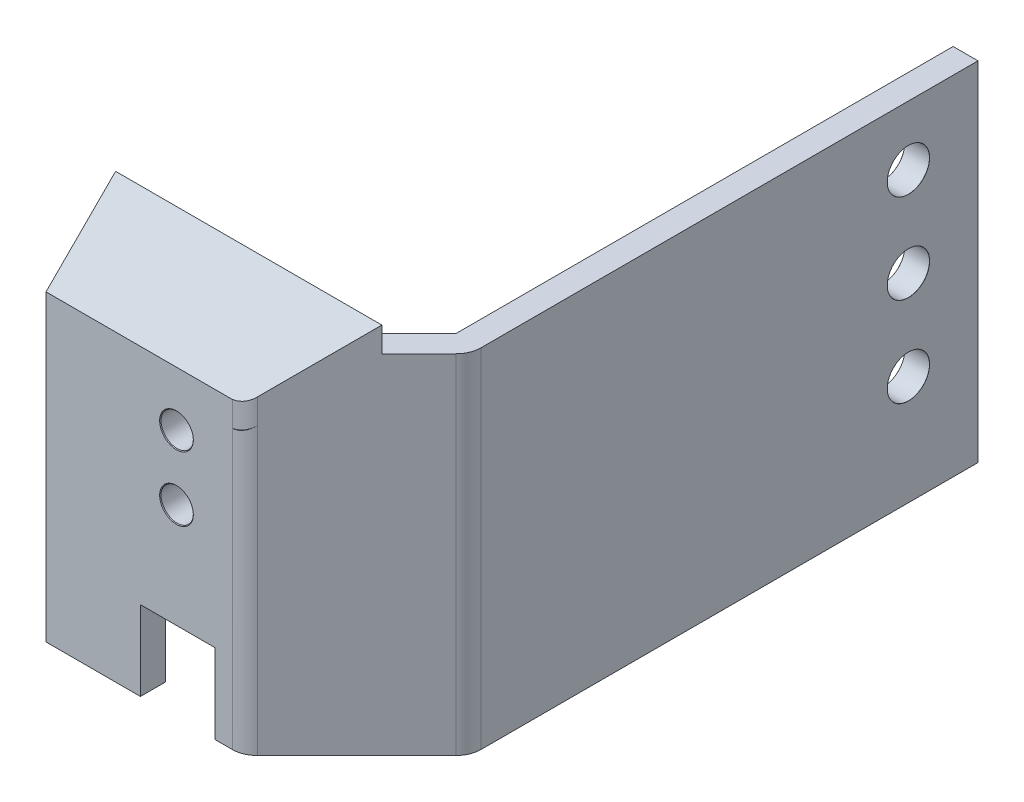
SolidWorks part; units mm, degrees
other "Pasta de soldas"
material "Liga de aço (SS)"
ref_plane "Plano frontal" through (0, 0, 0) normal (0, 0, 1) x (1, 0, 0)
ref_plane "Plano superior" through (0, 0, 0) normal (0, 1, 0) x (1, 0, 0)
ref_plane "Plano direito" through (0, 0, 0) normal (1, 0, 0) x (0, 0, -1)
sketch "Esboço15" plane through (0, 0, 0) normal (1, 0, 0) x (0, 0, -1)
  line L1 (0, 0) -> (200, 0)
  line L2 (0, 0) -> (0, 140)
  line L3 (0, 140) -> (200, 140)
  line L4 (200, 0) -> (200, 140)
  dimension "D1" = 200
  dimension "D2" = 140
base flange "Flange-base3" sketch "Esboço15" thickness 10 reverse thickness direction no parameters "D1"=10
sketch "Esboço22" plane through (0, 140, 0) normal (0, 1, 0) x (1, 0, 0)
  line L2 (-10, 0) -> (-50, -40)
  line L3 (-50, -40) -> (-125, -40)
  line L4 (-10, 200) -> (-10, 0) construction
  line L5 (-125, -40) -> (-125, -50)
  line L6 (-125, -50) -> (-50, -50)
  line L7 (-42.9289, -47.0711) -> (-2.9289, -7.0711)
  line L8 (-10, 0) -> (-2.9289, -7.0711) construction
  line L9 (-50, -40) -> (-42.9289, -47.0711) construction
  line L10 (-50, -40) -> (-50, -50) construction
  line L11 (-10, 0) -> (0, 0)
  arc A0 (-50, -50) -> (-42.9289, -47.0711) centre (-50, -40) ccw
  arc A1 (-2.9289, -7.0711) -> (0, 0) centre (-10, 0) ccw
  dimension "D2" = 75
  dimension "D3" = 45
  dimension "D4" = 10
  dimension "D5" = 10
  dimension "D1" = 40
extrude "Ressalto-extrusão3" add sketch "Esboço22" against normal up to surface (140 mm away) up to face at (-5, 0, -100)
sketch "Esboço28" plane through (0, 0, 0) normal (1, 0, 0) x (0, 0, -1)
  line L0 (-40, 122) -> (-22, 140)
  line L2 (-47.0711, 140) -> (-7.0711, 140) construction
  line L3 (-22, 140) -> (-40, 140)
  line L5 (-47.0711, 0) -> (-7.0711, 0) construction
  line L6 (-50, 0) -> (-50, 140) construction
  line L8 (-40, 140) -> (-50, 140)
  line L9 (-50, 140) -> (-50, 112)
  line L10 (-50, 112) -> (-40, 122)
  dimension "D1" = 122
  dimension "D2" = 45
  dimension "D3" = 10
extrude "Corte-extrusão1" cut sketch "Esboço28" against normal through all
sketch "Esboço29" plane through (0, 0, 50) normal (0, 0, 1) x (1, 0, 0)
  line L1 (-87, 32) -> (-57, 32)
  line L2 (-87, 32) -> (-87, 0)
  line L3 (-87, 0) -> (-57, 0)
  line L4 (-57, 32) -> (-57, 0)
  line L5 (-125, 0) -> (-50, 0) construction
  line L6 (-125, 112) -> (-50, 112) construction
  line L7 (-125, 0) -> (-125, 112) construction
  dimension "D1" = 30
  dimension "D2" = 80
  dimension "D3" = 38
extrude "Corte-extrusão2" cut sketch "Esboço29" against normal through all
hole_wizard "Furo com folga de M121" positions "Esboço30" profile "Esboço32" hole size "M12" standard "ISO" end condition through all
sketch "Esboço30" plane through (0, 0, 50) normal (0, 0, 1) x (1, 0, 0)
  line L0 (-125, 0) -> (-125, 112) construction
  line L1 (-57, 0) -> (-50, 0) construction
  point P0 (-72.5, 100)
  point P2 (-72.5, 74)
  dimension "D1" = 52.5
  dimension "D2" = 100
  dimension "D3" = 26
sketch "Esboço32" plane through (-72.5, 100, 50) normal (1, 0, 0) x (0, -1, 0)
  line L0 (0, 0) -> (0, 10)
  line L1 (0, 10) -> (6.525, 10)
  line L2 (6.5, 9.975) -> (6.5, 0.275)
  line L3 (6.5, 0.275) -> (6.775, 0)
  line L5 (6.775, 0) -> (0, 0)
  line L6 (-6.5, 0.275) -> (-6.775, 0) construction
  line L7 (6.525, 10) -> (6.5, 9.975)
  line L8 (-6.525, 10) -> (-6.5, 9.975) construction
  line L11 (0, -6.35) -> (0, 107.95) construction
  dimension "Thru Hole Dia." = 13
  dimension "Thru Hole Depth" = 10
  dimension "Near C'Sink Dia." = 13.55
  dimension "Near C'Sink Angle" = 90
  dimension "Far C'Sink Dia." = 13.05
  dimension "Far C'Sink Angle" = 90
sketch3d "3DSketch1"
  line L0 (-32, 140, 22) -> (-125, 140, 22)
  line L1 (-125, 140, 22) -> (-125, 112, 50)
  line L2 (-125, 112, 50) -> (-50, 112, 50)
  line L3 (-17.8579, 140, 22) -> (-42.9289, 114.9289, 47.0711)
  line L4 (-17.8579, 140, 22) -> (-32, 140, 22)
  line L5 (-125, 112, 50) -> (-125, 122, 40) construction
  arc A0 (-50, 112, 50) -> (-42.9289, 114.9289, 47.0711) centre (-51.0355, 118.9822, 43.0178) cw
  spline S1 degree 3 poles (-50, 112, 50) (-47.3124, 112, 50) (-44.8294, 113.0285, 48.9715) (-42.9289, 114.9289, 47.0711) knots 0 0 0 0 1 1 1 1 weights 1 0.949253 0.949253 1 construction
  point P8 (-51.0355, 126.0028, 50.0383)
extrude "Ressalto-extrusão4" add sketch "3DSketch1" along direction (0, 1, 0) on the side against the normal blind 10
hole_wizard "Furo com folga de M161" positions "Esboço34" profile "Esboço33" hole size "M16" standard "ISO" end condition through all
sketch "Esboço34" plane through (0, 0, 0) normal (1, 0, 0) x (0, 0, -1)
  line L0 (-40, 0) -> (-40, 122) construction
  line L1 (200, 140) -> (0, 140) construction
  line L2 (0, 0) -> (200, 0) construction
  line L4 (172, 116) -> (172, 80) construction
  line L5 (172, 80) -> (172, 44) construction
  point P0 (172, 116)
  point P2 (172, 80)
  point P4 (172, 44)
  dimension "D1" = 212
  dimension "D2" = 24
  dimension "D3" = 44
sketch "Esboço33" plane through (0, 116, -172) normal (0, 1, 0) x (0, 0, -1)
  line L0 (0, 0) -> (0, 10)
  line L1 (0, 10) -> (8.525, 10)
  line L2 (8.5, 9.975) -> (8.5, 0.025)
  line L3 (8.5, 0.025) -> (8.525, 0)
  line L5 (8.525, 0) -> (0, 0)
  line L6 (-8.5, 0.025) -> (-8.525, 0) construction
  line L7 (8.525, 10) -> (8.5, 9.975)
  line L8 (-8.525, 10) -> (-8.5, 9.975) construction
  line L11 (0, -6.35) -> (0, 107.95) construction
  dimension "Thru Hole Dia." = 17
  dimension "Thru Hole Depth" = 10
  dimension "Near C'Sink Dia." = 17.05
  dimension "Near C'Sink Angle" = 90
  dimension "Far C'Sink Dia." = 17.05
  dimension "Far C'Sink Angle" = 90
sketch "Esboço35" plane through (0, 140, 0) normal (0, 1, 0) x (1, 0, 0)
  line L0 (0, 0) -> (-125, 0)
  line L1 (-125, 0) -> (-125, -22)
  line L2 (-125, -22) -> (-17.8579, -22)
  line L3 (-17.8579, -22) -> (-2.9289, -7.0711)
  arc A0 (0, 0) -> (-2.9289, -7.0711) centre (-10, 0) cw
extrude "Ressalto-extrusão5" [suppressed] add sketch "Esboço35" along normal blind 10
mirror "Espelhar1" [suppressed]
delete or keep bodies "Corpo-Excluir/Manter 1" [suppressed] type delete bodies bodies 112
sketch "Bend-Lines3" [suppressed] plane through (0, 0, 0) normal (0, 1, 0) x (1, 0, 0)
sketch "Bounding-Box3" [suppressed] plane through (0, 0, 0) normal (0, 1, 0) x (1, 0, 0)
sheet metal parameters "Sheet-Metal5" thickness 10 parameters "D1"=10
flat pattern "Flat-Pattern5" [suppressed]
sketch "Bend-Lines5" plane through (0, 0, 0) normal (1, 0, 0) x (0, 0, -1)
sketch3d "Bounding-Box5" [suppressed]
  line L0 (190, 0, 0) -> (0, 0, 0) construction
  line L1 (190, 120, 0) -> (0, 120, 0) construction
  line L2 (190, 0, 0) -> (190, 120, 0) construction
  line L3 (0, 0, 0) -> (0, 120, 0) construction
sheet metal parameters "Sheet-Metal7" thickness 10 parameters "D1"=10
flat pattern "Flat-Pattern5"
sketch "Bend-Lines5" plane through (0, 0, 0) normal (1, 0, 0) x (0, 0, -1)
sketch3d "Bounding-Box5" [suppressed]
  line L0 (190, 0, 0) -> (0, 0, 0) construction
  line L1 (190, 140, 0) -> (0, 140, 0) construction
  line L2 (190, 0, 0) -> (190, 140, 0) construction
  line L3 (0, 0, 0) -> (0, 140, 0) construction
sheet metal parameters "Sheet-Metal8" thickness 10 parameters "D1"=10
flat pattern "Flat-Pattern5"
sketch "Bend-Lines5" plane through (0, 0, 0) normal (1, 0, 0) x (0, 0, -1)
sketch3d "Bounding-Box5" [suppressed]
  line L0 (190, 0, 0) -> (0, 0, 0) construction
  line L1 (190, 140, 0) -> (0, 140, 0) construction
  line L2 (190, 0, 0) -> (190, 140, 0) construction
  line L3 (0, 0, 0) -> (0, 140, 0) construction
sheet metal parameters "Sheet-Metal9" thickness 10 parameters "D1"=10
flat pattern "Flat-Pattern5"
sketch "Bend-Lines5" plane through (0, 0, 0) normal (1, 0, 0) x (0, 0, -1)
sketch3d "Bounding-Box5" [suppressed]
  line L0 (190, 0, 0) -> (0, 0, 0) construction
  line L1 (190, 140, 0) -> (0, 140, 0) construction
  line L2 (190, 0, 0) -> (190, 140, 0) construction
  line L3 (0, 0, 0) -> (0, 140, 0) construction
sheet metal parameters "Sheet-Metal10" thickness 10 parameters "D1"=10
flat pattern "Flat-Pattern5"
sketch "Bend-Lines5" plane through (0, 0, 0) normal (1, 0, 0) x (0, 0, -1)
sketch3d "Bounding-Box5" [suppressed]
  line L0 (190, 0, 0) -> (0, 0, 0) construction
  line L1 (190, 140, 0) -> (0, 140, 0) construction
  line L2 (190, 0, 0) -> (190, 140, 0) construction
  line L3 (0, 0, 0) -> (0, 140, 0) construction
sheet metal parameters "Sheet-Metal11" thickness 10 parameters "D1"=10
flat pattern "Flat-Pattern5"
sketch "Bend-Lines5" plane through (0, 0, 0) normal (1, 0, 0) x (0, 0, -1)
sketch3d "Bounding-Box5" [suppressed]
  line L0 (190, 0, 0) -> (0, 0, 0) construction
  line L1 (190, 140, 0) -> (0, 140, 0) construction
  line L2 (190, 0, 0) -> (190, 140, 0) construction
  line L3 (0, 0, 0) -> (0, 140, 0) construction
sheet metal parameters "Sheet-Metal12" thickness 10 parameters "D1"=10
flat pattern "Flat-Pattern5"
sketch "Bend-Lines5" plane through (0, 0, 0) normal (1, 0, 0) x (0, 0, -1)
sketch3d "Bounding-Box5" [suppressed]
  line L0 (200, 0, 0) -> (0, 0, 0) construction
  line L1 (200, 140, 0) -> (0, 140, 0) construction
  line L2 (200, 0, 0) -> (200, 140, 0) construction
  line L3 (0, 0, 0) -> (0, 140, 0) construction
sheet metal parameters "Sheet-Metal13" thickness 10 parameters "D1"=10
flat pattern "Flat-Pattern13"
sketch "Bend-Lines7" plane through (0, 0, 0) normal (0, 1, 0) x (1, 0, 0)
sketch3d "Bounding-Box7" [suppressed]
  line L0 (200, 140, 0) -> (0, 140, 0) construction
  line L1 (200, 0, 0) -> (0, 0, 0) construction
  line L2 (200, 140, 0) -> (200, 0, 0) construction
  line L3 (0, 140, 0) -> (0, 0, 0) construction
sheet metal parameters "Sheet-Metal14" thickness 10 parameters "D1"=10
flat pattern "Flat-Pattern5"
sketch "Bend-Lines5" plane through (0, 0, 0) normal (1, 0, 0) x (0, 0, -1)
sketch3d "Bounding-Box5" [suppressed]
  line L0 (200, 0, 0) -> (0, 0, 0) construction
  line L1 (200, 140, 0) -> (0, 140, 0) construction
  line L2 (200, 0, 0) -> (200, 140, 0) construction
  line L3 (0, 0, 0) -> (0, 140, 0) construction
equation "\"D2@Esboço15\"=120.00mm+20"
equation "\"D2@Esboço22\"=40+35.00mm"
equation "\"D1@Esboço30\"=12.50mm+40"
